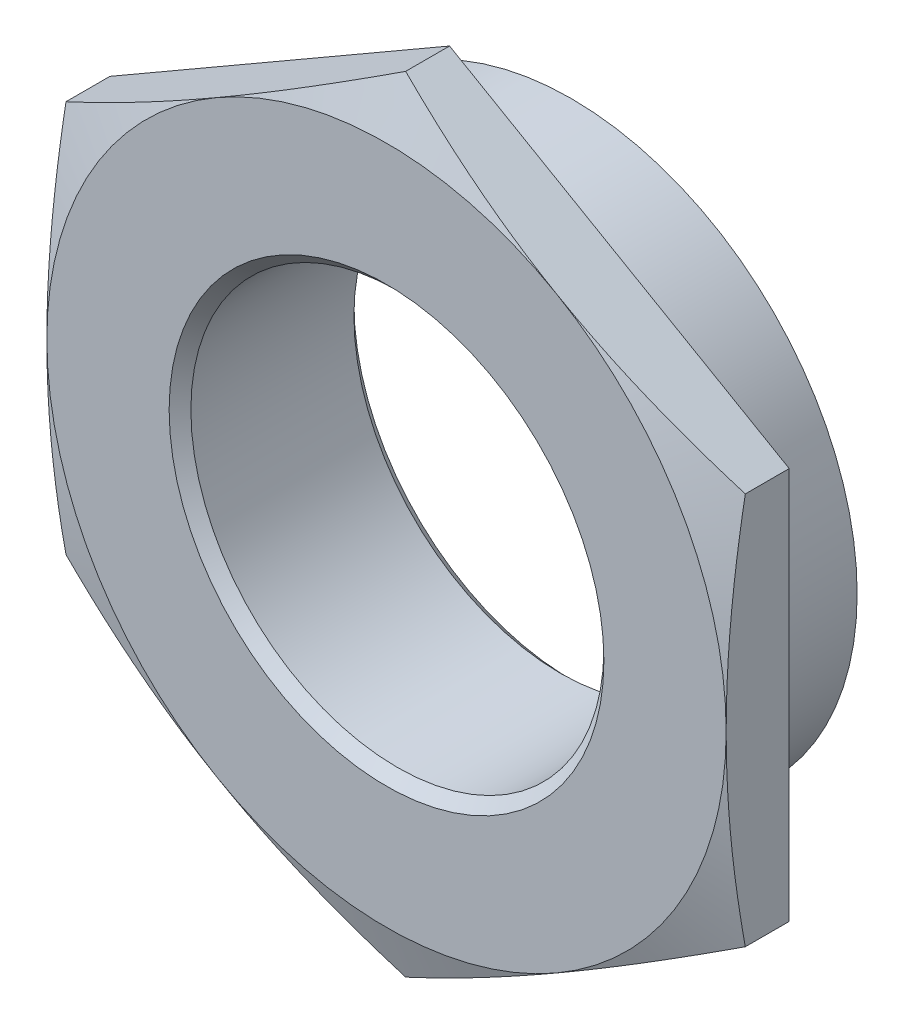
SolidWorks part; units mm, degrees
ref_plane "Front Plane" through (0, 0, 0) normal (0, 0, 1) x (1, 0, 0)
ref_plane "Top Plane" through (0, 0, 0) normal (0, 1, 0) x (1, 0, 0)
ref_plane "Right Plane" through (0, 0, 0) normal (1, 0, 0) x (0, 0, -1)
sketch "Sketch1" plane through (0, 0, 0) normal (0, 0, 1) x (1, 0, 0)
  line L1 (0, 4.5827) -> (-3.9687, 2.2914)
  line L2 (-3.9687, 2.2914) -> (-3.9687, -2.2914)
  line L3 (-3.9687, -2.2914) -> (0, -4.5827)
  line L4 (0, -4.5827) -> (3.9687, -2.2914)
  line L5 (3.9687, -2.2914) -> (3.9687, 2.2914)
  line L6 (3.9687, 2.2914) -> (0, 4.5827)
  circle A0 centre (0, 0) radius 3.9688 construction
  circle A1 centre (0, 0) radius 3.9688 construction
  dimension "A" = 7.9375
extrude "Extrude1" add sketch "Sketch1" against normal blind 2.159
sketch "Sketch14" plane through (0, 0, -2.159) normal (0, 0, -1) x (-1, 0, 0)
  circle A0 centre (0, 0) radius 3.3401
  dimension "C" = 6.6802
extrude "Cut-Extrude7" cut sketch "Sketch14" against normal offset from surface (1.4224 mm away) 0.7366 flip side to cut up to face at (0, 0, 0)
sketch "Sketch7" plane through (0, 0, 0) normal (0, 0, 1) x (1, 0, 0)
  circle A0 centre (0, 0) radius 2.413
  dimension "Thread Od" = 4.826
extrude "Cut-Extrude3" cut sketch "Sketch7" against normal through all
sketch "Sketch15" plane through (0, 0, -2.159) normal (0, 0, -1) x (-1, 0, 0)
  circle A0 centre (0, 0) radius 2.413 construction
  circle A1 centre (0, 0) radius 2.413
curve "Helix/Spiral1" pitch 0.7937 height 5.334 turns 6.72 parameters "pitch"=0.7937
sketch "Sketch9" plane through (0, 0, 0) normal (1, 0, 0) x (0, 0, -1)
  line L0 (2.8535, 2.413) -> (2.5559, 1.8974)
  line L1 (2.5559, 1.8974) -> (2.4567, 1.8974)
  line L2 (2.4567, 1.8974) -> (2.159, 2.413)
  line L3 (2.8535, 2.413) -> (2.159, 2.413)
  line L4 (2.5063, 2.413) -> (2.5063, 1.8974) construction
  line L5 (2.7047, 2.1552) -> (2.3078, 2.1552) construction
  line L7 (2.159, -2.413) -> (2.159, 2.413) construction
  dimension "D1" = 60
  dimension "D2" = 0.0992
  dimension "D3" = 0.3969
sweep "Sweep1" [suppressed] add profiles "Sketch9" path "Helix/Spiral1"
sketch "Sketch10" plane through (0, 0, 0) normal (0, 0, 1) x (1, 0, 0)
  line L6 (3.9687, 2.2914) -> (0, 4.5827)
  line L7 (3.9687, 2.2914) -> (0, 4.5827)
  line L8 (0, 4.5827) -> (-3.9687, 2.2914)
  line L9 (0, 4.5827) -> (-3.9687, 2.2914)
  line L10 (-3.9687, 2.2914) -> (-3.9687, -2.2914)
  line L11 (-3.9687, 2.2914) -> (-3.9687, -2.2914)
  line L12 (-3.9687, -2.2914) -> (0, -4.5827)
  line L13 (-3.9687, -2.2914) -> (0, -4.5827)
  line L14 (0, -4.5827) -> (3.9687, -2.2914)
  line L15 (0, -4.5827) -> (3.9687, -2.2914)
  line L16 (3.9687, -2.2914) -> (3.9687, 2.2914)
  line L17 (3.9687, -2.2914) -> (3.9687, 2.2914)
  dimension "D1" = 0
extrude "Cut-Extrude4" [suppressed] cut sketch "Sketch10" along normal through all
sketch "Sketch16" plane through (0, 0, -2.159) normal (0, 0, -1) x (-1, 0, 0)
  circle A0 centre (0, 0) radius 3.3401 construction
  circle A1 centre (0, 0) radius 3.3401
extrude "Cut-Extrude8" [suppressed] cut sketch "Sketch16" along normal through all
sketch "Sketch13" plane through (0, 0, 0) normal (0, 0, 1) x (1, 0, 0)
  circle A2 centre (0, 0) radius 2.54
  circle A3 centre (0, 0) radius 2.54
  dimension "D1" = 0.127
extrude "Cut-Extrude6" cut sketch "Sketch13" against normal through all draft 45
sketch "Sketch17" plane through (0, 0, -2.159) normal (0, 0, -1) x (-1, 0, 0)
  circle A1 centre (0, 0) radius 2.54
  circle A2 centre (0, 0) radius 2.54
  dimension "D1" = 0
extrude "Cut-Extrude11" cut sketch "Sketch17" against normal through all draft 45
sketch "Sketch20" plane through (0, 0, 0) normal (0, 0, 1) x (1, 0, 0)
  circle A0 centre (0, 0) radius 3.9688 construction
  circle A1 centre (0, 0) radius 3.9688
extrude "Cut-Extrude13" cut sketch "Sketch20" against normal through all draft 70 flip side to cut
equation "\"D3@Helix/Spiral1\" = \"B@Extrude1\"+.125"
equation "\"D2@Sketch9\" = \"pitch@Helix/Spiral1\"*.125"
equation "\"D3@Sketch9\" = \"pitch@Helix/Spiral1\"*.5"
